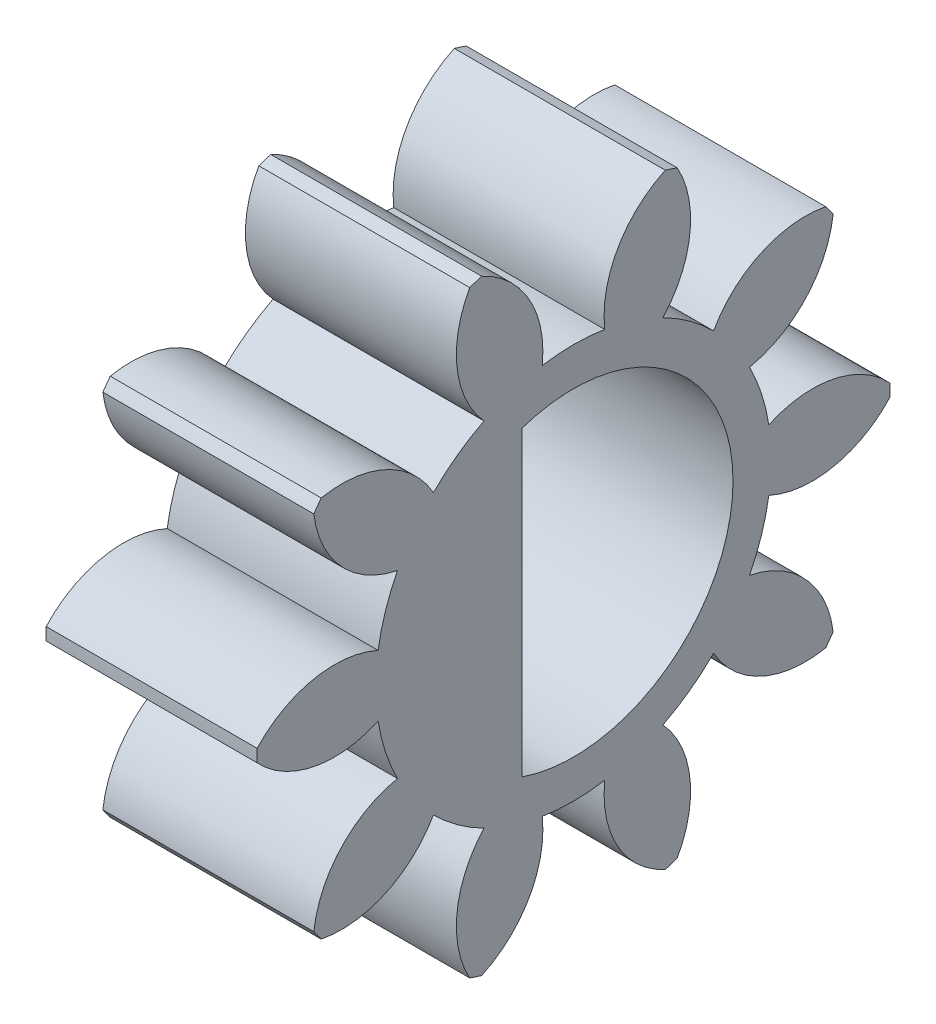
SolidWorks part; units mm, degrees
ref_plane "Plane1" through (0, 0, 0) normal (0, 0, 1) x (1, 0, 0)
ref_plane "Plane2" through (0, 0, 0) normal (0, 1, 0) x (1, 0, 0)
ref_plane "Plane3" through (0, 0, 0) normal (1, 0, 0) x (0, 0, -1)
other "Configuration Table"
sketch "HoldingSke" plane through (0, 0, 0) normal (0, 1, 0) x (1, 0, 0)
  line L0 (0, 0) -> (0.9848, -0.1736)
  line L1 (-15, 0) -> (100, 0) construction
  line L2 (0, 0) -> (-2.1039, 2.3779)
  line L3 (0, 0) -> (-11.863, 4.5341)
  line L4 (0, 0) -> (8.5048, 1.4996)
  line L5 (0, 0) -> (-46.8476, -17.4728)
  line L6 (0, 0) -> (-3.3159, -2.2372)
  line L7 (-2.1039, 2.3779) -> (8.6586, 51.2059)
  line L8 (-76.2, 54.61) -> (-75.2, 54.61)
  line L9 (-71.009, 38.7566) -> (-53.1078, 45.2721)
  line L10 (-76.2, 71.12) -> (104.1128, 71.12)
  line L11 (0, 0) -> (-4, 0)
  line L12 (-76.2, 101.6) -> (-76.162, 101.6)
  line L13 (24.9733, 27.94) -> (52.9518, 28.4284)
  line L14 (24.9733, 27.94) -> (24.9743, 27.94)
  line L15 (24.9733, 27.94) -> (100.4006, 29.5858)
  line L16 (-63.627, -1) -> (-12.827, -1)
  circle A0 centre (0, 0) radius 3
  circle A1 centre (0, 0) radius 3.749
  circle A2 centre (0, 0) radius 37.5
  circle A3 centre (0, 0) radius 3
  dimension "Num_teeth" = 10
  dimension "Pitch_radius" = 180.3128
  dimension "Width" = 4
  dimension "Thickness" = 4
sketch "BasProSke" plane through (0, 0, 0) normal (0, 1, 0) x (1, 0, 0)
  line L0 (-10, 0) -> (60, 0) construction
  line L1 (0, 0) -> (0, 6)
  line L2 (0, 0) -> (4, 0)
  line L3 (4, 0) -> (4, 6)
  line L4 (4, 6) -> (0, 6)
  dimension "Thickness" = 4
  dimension "Diameter" = 12
revolve "Base-Revolve" add sketch "BasProSke" angle 360 about L0
sketch "TooCutSke" plane through (0, 0, 0) normal (1, 0, 0) x (0, 0, -1)
  line L1 (0, 0) -> (0, 107) construction
  line L2 (0, 0) -> (-0.8485, 4.9275) construction
  line L3 (0, 0) -> (-3.0584, 9.4126) construction
  line L4 (-0.8485, 4.9275) -> (-1.5292, 4.7063) construction
  arc A0 (0.5928, 3.7018) -> (-0.5928, 3.7018) centre (0, 0) ccw
  arc A1 (1.7758, 5.7578) -> (-1.7758, 5.7578) centre (0, 0) ccw
  circle A2 centre (0, 0) radius 5 construction
  circle A3 centre (0, 0) radius 4.6985 construction
  arc A4 (-0.5928, 3.7018) -> (-1.7758, 5.7578) centre (-2.5801, 3.9267) ccw
  arc A5 (1.7758, 5.7578) -> (0.5928, 3.7018) centre (2.5801, 3.9267) ccw
extrude "ToothCut" cut sketch "TooCutSke" along normal through all
fillet "Breaks" [suppressed] radius 0.02 tangent propagation no
fillet "RootFillets" [suppressed] radius 0.251
pattern_circular "TeethCuts" count 10 every 36 about axis through (-10, 0, 0) along (1, 0, 0) of "ToothCut", "RootFillets", "Breaks"
sketch "HubNeaOneSke" plane through (0, 0, 0) normal (-1, 0, 0) x (0, 0, 1)
  circle A0 centre (0, 0) radius 3.749
  dimension "Diameter" = 7.498
extrude "HubNearOne" [suppressed] add sketch "HubNeaOneSke" along normal blind 46.0001
sketch "HubNeaBotSke" plane through (0, 0, 0) normal (-1, 0, 0) x (0, 0, 1)
  circle A0 centre (0, 0) radius 3.749
  dimension "Diameter" = 7.498
extrude "HubNearBoth" [suppressed] add sketch "HubNeaBotSke" along normal blind 23
ref_plane "FarPln" through (4, 0, 0) normal (1, 0, 0) x (0, 0, -1)
sketch "HubFarSke" plane through (4, 0, 0) normal (1, 0, 0) x (0, 0, -1)
  circle A0 centre (0, 0) radius 3.749
  dimension "Diameter" = 7.498
extrude "HubFar" [suppressed] add sketch "HubFarSke" along normal blind 23
sketch "BorSke" plane through (0, 0, 0) normal (1, 0, 0) x (0, 0, -1)
  circle A0 centre (0, 0) radius 3.025
  dimension "Diameter" = 6.05
extrude "Bore" cut sketch "BorSke" along normal mid plane 100.0001
sketch "KeySke" plane through (0, 0, 0) normal (1, 0, 0) x (0, 0, -1)
  line L0 (-1, 0) -> (-1, 4)
  line L1 (-1, 4) -> (1, 4)
  line L2 (1, 4) -> (1, 0)
  line L3 (0, 0) -> (0, 34) construction
  line L4 (-1, 0) -> (1, 0)
  dimension "Width" = 2
extrude "Keyway" [suppressed] cut sketch "KeySke" along normal mid plane 100.0001
pattern_circular "Keyway2" [suppressed] count 2 every 90 about axis through (-10, 0, 0) along (1, 0, 0)
ref_axis "Axis1" through (4, 0, 0) along (-1, 0, 0)
sketch "Sketch2" plane through (0, 0, 0) normal (-1, 0, 0) x (0, 0, 1)
  circle A0 centre (0, 0) radius 3.025
  dimension "D1" = 6.05
sketch "Sketch1" plane through (0, 0, 0) normal (-1, 0, 0) x (0, 0, 1)
  line L0 (0.975, 2.8636) -> (0.975, -2.8636)
  line L1 (0.975, 0) -> (-3.025, 0) construction
  circle A0 centre (0, 0) radius 3.025 construction
  arc A1 (0.975, 2.8636) -> (0.975, -2.8636) centre (0, 0) cw
  circle M2 centre (0, 0) radius 3.025
  dimension "D1" = 4
extrude "Boss-Extrude1" add sketch "Sketch1" against normal up to surface (4 mm away) contours L0 M2 region at (0, 0, 1.8247) up to face at (4, 0, 3.025)
equation "' \"Module@HoldingSke\" = 6.35"
equation "' \"Num_teeth@HoldingSke\" = 12"
equation "' \"Ap@HoldingSke\" =  20"
equation "' \"Ap@HoldingSke\" = 20"
equation "' \"Width@HoldingSke\" = 0.5 * 25.4"
equation "' \"Hub_dia@HoldingSke\"= 1 * 25.4"
equation "' \"Hub_dia@HoldingSke\" = 1 * 25.4"
equation "' \"Overall_len@HoldingSke\" = 1.0 * 25.4"
equation "' \"Bore@HoldingSke\" = 0.75 * 25.4"
equation "' \"T_dim@HoldingSke\" = 0.1 * 25.4"
equation "' \"Width@KeySke\" = 0.25 * 25.4"
equation "' \"Show_teeth@HoldingSke\" = 13"
equation "' \"Backlash@HoldingSke\" = 0.009 * 25.4"
equation "' \"Addendum_fac@HoldingSke\" = 1.0"
equation "' \"Dedendum_fac@HoldingSke\" = 1.25"
equation "' \"Dedendum_add@HoldingSke\" = 0.00005 * 25.4"
equation "' \"Clearance_fac@HoldingSke\" = 0.25"
equation "\"Pitch@HoldingSke\" = 1 / \"Module@HoldingSke\""
equation "\"Overcut_dia@TooCutSke\" = (\"Num_teeth@HoldingSke\" + 2 * \"Addendum_fac@HoldingSke\") / \"Pitch@HoldingSke\" + 0.002 * 25.4"
equation "\"Pitch_dia@TooCutSke\" = \"Num_teeth@HoldingSke\" / \"Pitch@HoldingSke\""
equation "\"Base_dia@TooCutSke\" = \"Num_teeth@HoldingSke\" / \"Pitch@HoldingSke\" * cos((\"Ap@HoldingSke\"  * 3.14159265 / 180))"
equation "\"Root_dia@TooCutSke\" = (\"Num_teeth@HoldingSke\" + 2) / \"Pitch@HoldingSke\" - 2 * (\"Addendum_fac@HoldingSke\" + \"Dedendum_fac@HoldingSke\") / \"Pitch@HoldingSke\" - \"Dedendum_add@HoldingSke\" * 2"
equation "\"Half_ang@TooCutSke\" = 180 / \"Num_teeth@HoldingSke\""
equation "\"Half_CT@TooCutSke\" = \"Num_teeth@HoldingSke\" / \"Pitch@HoldingSke\" * sin((3.14159265 / 2 / \"Num_teeth@HoldingSke\")) / 2 - 7 * \"Backlash@HoldingSke\" / 4"
equation "\"Flank_rad@TooCutSke\" = \"Num_teeth@HoldingSke\" / \"Pitch@HoldingSke\" / 5"
equation "\"Radius@RootFillets\" = \"Clearance_fac@HoldingSke\" / \"Pitch@HoldingSke\" + \"Dedendum_add@HoldingSke\""
equation "\"Break_rad@Breaks\" = 0.02 / \"Pitch@HoldingSke\""
equation "\"Thickness@HoldingSke\" = \"Width@HoldingSke\""
equation "\"OAL@HoldingSke\" = \"Thickness@HoldingSke\""
equation "\"MHD@HoldingSke\" = (\"Num_teeth@HoldingSke\" + 2) / \"Pitch@HoldingSke\" - 2 * (\"Addendum_fac@HoldingSke\" + \"Dedendum_fac@HoldingSke\")  / \"Pitch@HoldingSke\" - \"Dedendum_add@HoldingSke\" * 2"
equation "\"MBD@HoldingSke\" = (\"Num_teeth@HoldingSke\" + 2) / \"Pitch@HoldingSke\" - 2 * (\"Addendum_fac@HoldingSke\" + \"Dedendum_fac@HoldingSke\")  / \"Pitch@HoldingSke\" - \"Dedendum_add@HoldingSke\" * 2 - 0.002 * 25.4"
equation "\"MHD@HoldingSke\" = ((sgn( \"MHD@HoldingSke\" - \"Hub_dia@HoldingSke\" )-1)*( \"MHD@HoldingSke\" - \"Hub_dia@HoldingSke\" ))/-2+ \"Hub_dia@HoldingSke\""
equation "\"MBD@HoldingSke\" = ((sgn( \"MBD@HoldingSke\" - \"Bore@HoldingSke\" )-1)*( \"MBD@HoldingSke\" - \"Bore@HoldingSke\" ))/-2+ \"Bore@HoldingSke\""
equation "\"OAL@HoldingSke\" = ((sgn( \"OAL@HoldingSke\" - \"Overall_len@HoldingSke\" )+1)*( \"OAL@HoldingSke\" - \"Overall_len@HoldingSke\" ))/2 + \"Overall_len@HoldingSke\" + 0.000002 * 25.4"
equation "\"Num_teeth@TeethCuts\" = int( \"Show_teeth@HoldingSke\" ) + 1"
equation "\"Num_teeth@TeethCuts\" = ((sgn( \"Num_teeth@TeethCuts\" - \"Num_teeth@HoldingSke\" )-1)*( \"Num_teeth@TeethCuts\" - \"Num_teeth@HoldingSke\" ))/-2+ \"Num_teeth@HoldingSke\""
equation "\"Num_teeth@TeethCuts\" = ((sgn( \"Num_teeth@TeethCuts\" - 2.0)+1)*( \"Num_teeth@TeethCuts\" - 2.0))/2 +2.0"
equation "\"Angle@TeethCuts\" = 360.0 / \"Num_teeth@HoldingSke\""
equation "\"Diameter@BasProSke\" = (\"Num_teeth@HoldingSke\" + 2 * \"Addendum_fac@HoldingSke\") / \"Pitch@HoldingSke\""
equation "\"Thickness@BasProSke\"  = \"Thickness@HoldingSke\""
equation "' \"Fillet_rad@BasProSke\" =  \"Thickness@HoldingSke\" * 0.05"
equation "' \"Fillet_rad@BasProSke\" = \"Thickness@HoldingSke\" * 0.05"
equation "\"MHD@HoldingSke\" = ((sgn( \"MHD@HoldingSke\" - \"Root_dia@TooCutSke\" )-1)*( \"MHD@HoldingSke\" - \"Root_dia@TooCutSke\" ))/-2+ \"Root_dia@TooCutSke\""
equation "\"Diameter@HubNeaOneSke\" = \"MHD@HoldingSke\""
equation "\"Length@HubNearOne\" = \"OAL@HoldingSke\" - \"Thickness@BasProSke\""
equation "\"Diameter@HubNeaBotSke\" = \"MHD@HoldingSke\""
equation "\"Length@HubNearBoth\" = ( \"OAL@HoldingSke\" - \"Thickness@BasProSke\" ) / 2.0"
equation "\"Thickness@FarPln\" = \"Thickness@BasProSke\""
equation "\"Diameter@HubFarSke\" = \"MHD@HoldingSke\""
equation "\"Length@HubFar\" = ( \"OAL@HoldingSke\" - \"Thickness@BasProSke\" ) / 2.0"
equation "\"Diameter@BorSke\"=6.05"
equation "\"D1@Bore\" = \"OAL@HoldingSke\" * 2.0"
equation "\"D1@Keyway\" = \"OAL@HoldingSke\" * 2.0"
equation "\"Offset@KeySke\" = \"T_dim@HoldingSke\" + \"MBD@HoldingSke\" / 2.0"
